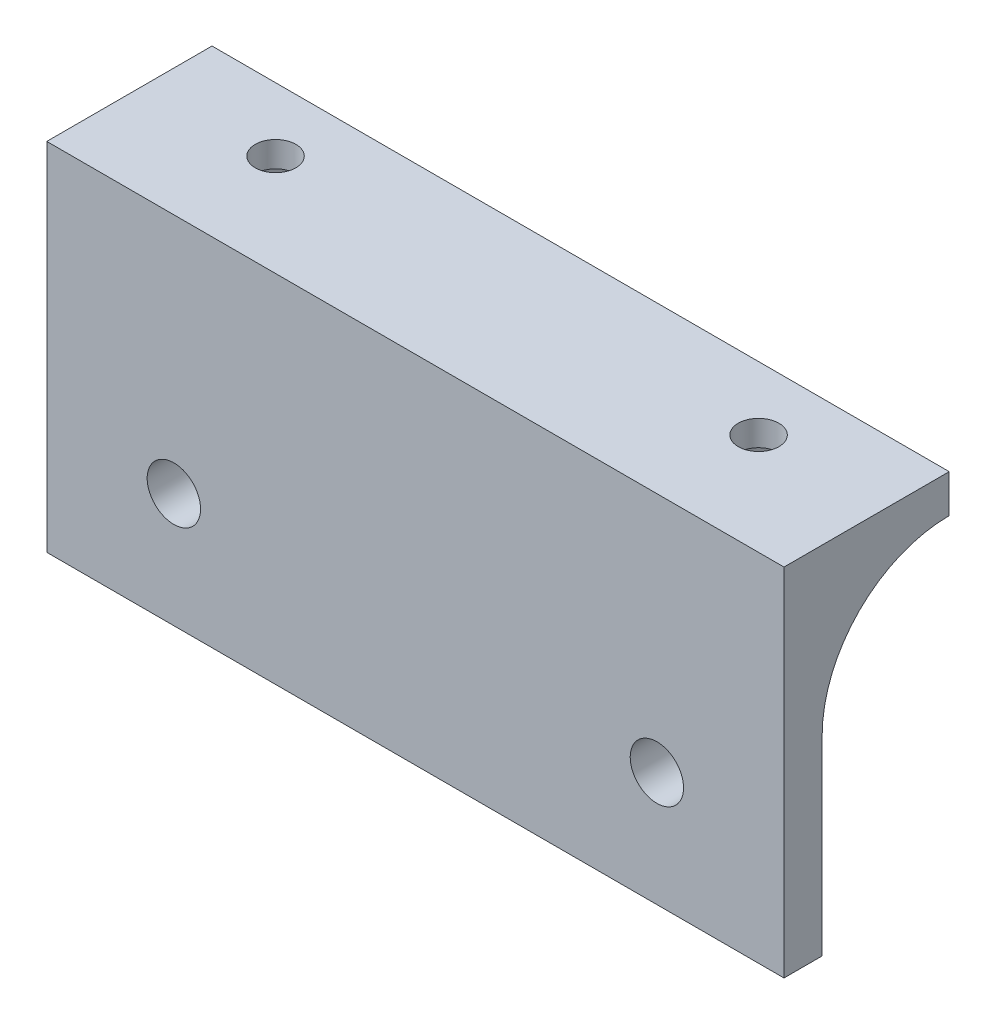
SolidWorks part; units mm, degrees
ref_plane "Front Plane" through (0, 0, 0) normal (0, 0, 1) x (1, 0, 0)
ref_plane "Top Plane" through (0, 0, 0) normal (0, 1, 0) x (1, 0, 0)
ref_plane "Right Plane" through (0, 0, 0) normal (1, 0, 0) x (0, 0, -1)
sketch "Rigidbot" plane through (0, 0, 0) normal (0, 0, 1) x (1, 0, 0)
  line L0 (-29, -5) -> (29, -5) construction
  line L1 (-29, 14) -> (29, 14)
  line L2 (-29, 14) -> (-29, -14)
  line L3 (-29, -14) -> (29, -14)
  line L4 (29, 14) -> (29, -14)
  line L5 (-29, 14) -> (29, -14) construction
  line L6 (-29, -14) -> (29, 14) construction
  line L7 (0, 14) -> (0, -14) construction
  circle A0 centre (-19, -5) radius 2.1
  circle A1 centre (19, -5) radius 2.1
  point P0 (0, 0)
  dimension "D3" = 4.2
  dimension "D1" = 58
  dimension "D2" = 38
  dimension "D4" = 9
  dimension "D5" = 28
extrude "Boss-Rigidbot" add sketch "Rigidbot" along normal blind 3
sketch "Case" plane through (0, 14, 0) normal (0, 1, 0) x (1, 0, 0)
  line L0 (-29, -3) -> (29, -3)
  line L1 (29, -3) -> (29, 10)
  line L2 (29, 10) -> (-29, 10)
  line L3 (-29, 10) -> (-29, -3)
  line L4 (-29, 5) -> (29, 5) construction
  line L5 (0, 10) -> (0, -3) construction
  circle A0 centre (-19, 5) radius 1.6
  circle A1 centre (19, 5) radius 1.6
  dimension "D1" = 3.2
  dimension "D2" = 38
  dimension "D3" = 5
  dimension "D4" = 8
extrude "Boss-Case" add sketch "Case" against normal blind 3
sketch "M3Nut" plane through (0, 14, 0) normal (0, 1, 0) x (1, 0, 0)
  line L0 (0, 10) -> (0, -3) construction
  line L1 (-15.7668, 5) -> (-17.3834, 7.8)
  line L2 (-17.3834, 7.8) -> (-20.6166, 7.8)
  line L3 (-20.6166, 7.8) -> (-22.2332, 5)
  line L4 (-22.2332, 5) -> (-20.6166, 2.2)
  line L5 (-20.6166, 2.2) -> (-17.3834, 2.2)
  line L6 (-17.3834, 2.2) -> (-15.7668, 5)
  line L7 (29, 10) -> (-29, 10) construction
  line L8 (29, -3) -> (-29, -3) construction
  line L9 (17.3834, 2.2) -> (15.7668, 5)
  line L10 (20.6166, 2.2) -> (17.3834, 2.2)
  line L11 (22.2332, 5) -> (20.6166, 2.2)
  line L12 (20.6166, 7.8) -> (22.2332, 5)
  line L13 (17.3834, 7.8) -> (20.6166, 7.8)
  line L14 (15.7668, 5) -> (17.3834, 7.8)
  circle A0 centre (-19, 5) radius 2.8 construction
  circle A1 centre (19, 5) radius 2.8 construction
  dimension "D1" = 5.6
extrude "Cut-M3Nut" cut sketch "M3Nut" against normal blind 10 from offset 2 offset against normal yes
fillet "Fillet" radius 10 1 edges at (0, 11, 0)
